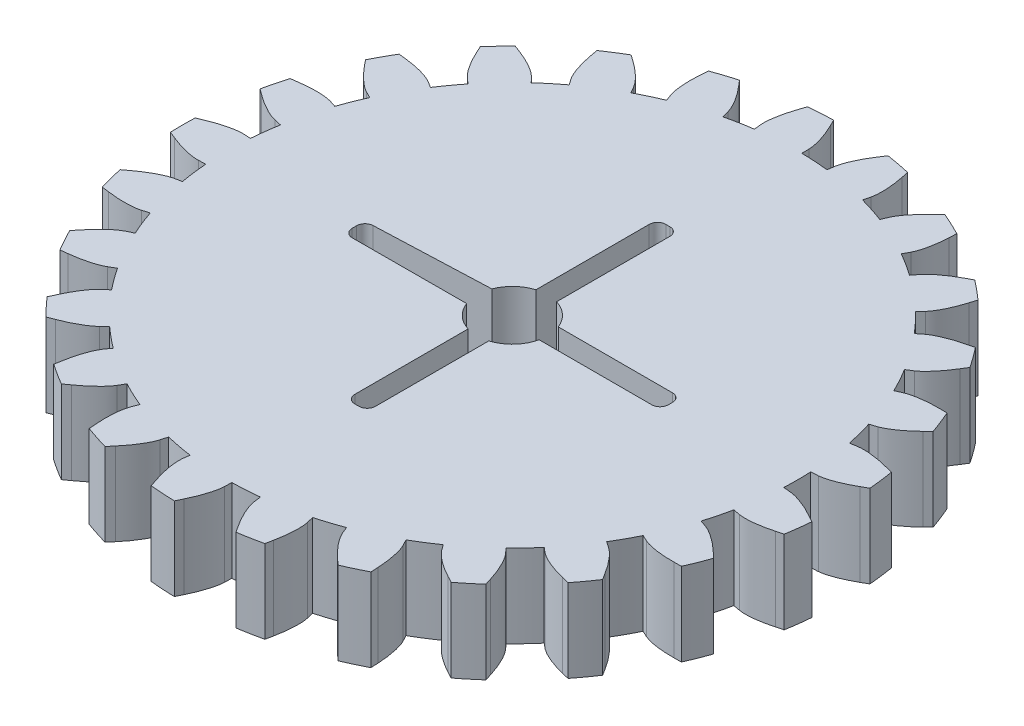
SolidWorks part; units mm, degrees
ref_plane "Front Plane" through (0, 0, 0) normal (0, 0, 1) x (1, 0, 0)
ref_plane "Top Plane" through (0, 0, 0) normal (0, 1, 0) x (1, 0, 0)
ref_plane "Right Plane" through (0, 0, 0) normal (1, 0, 0) x (0, 0, -1)
sketch "Sketch1" plane through (0, 0, 0) normal (0, 1, 0) x (1, 0, 0)
  line L0 (0, 30) -> (-129.8026, 30) construction
  line L1 (-99.777, -6.3159) -> (118.111, 72.9889) construction
  circle A0 centre (0, 0) radius 30
  circle A1 centre (0, 0) radius 28.1908
  dimension "D1" = 60
  dimension "D2" = 20
sketch "Sketch2" plane through (0, 0, 0) normal (0, 1, 0) x (1, 0, 0)
  line L0 (0, 0) -> (-9.6418, 26.4907) construction
  line L1 (-99.777, -6.3159) -> (118.111, 72.9889) construction
  line L2 (-9.6418, 26.4907) -> (0, 30)
  line L3 (-10.3543, 26.2204) -> (0, 0) construction
  line L4 (-10.3543, 26.2204) -> (-0.1021, 30.2689) construction
  line L5 (0, 0) -> (-11.0591, 25.931) construction
  line L6 (0, 0) -> (-11.7559, 25.6226) construction
  line L7 (-12.4441, 25.2955) -> (0, 0) construction
  line L8 (0, 0) -> (-13.1232, 24.95) construction
  line L9 (-8.9223, 26.7416) -> (0.088, 29.7479) construction
  line L10 (-11.0591, 25.931) -> (-0.2192, 30.554) construction
  line L11 (-11.7559, 25.6226) -> (-0.3523, 30.8547) construction
  line L12 (-12.4441, 25.2955) -> (-0.5023, 31.1703) construction
  line L13 (-6.7269, 27.3764) -> (0.2773, 29.0975) construction
  line L14 (-7.4643, 27.1846) -> (0.2256, 29.2961) construction
  line L15 (-5.9846, 27.5482) -> (0.319, 28.9176) construction
  line L16 (-8.1963, 26.973) -> (0.1629, 29.5131) construction
  line L17 (-5.2378, 27.6999) -> (0.3517, 28.7569) construction
  circle A0 centre (0, 0) radius 28.1908 construction
  arc A1 (-9.6418, 26.4907) -> (-10.3543, 26.2204) centre (0, 0) ccw
  arc A2 (-10.3543, 26.2204) -> (-11.0591, 25.931) centre (0, 0) ccw
  arc A3 (-11.0591, 25.931) -> (-11.7559, 25.6226) centre (0, 0) ccw
  arc A4 (-11.7559, 25.6226) -> (-12.4441, 25.2955) centre (0, 0) ccw
  arc A5 (-12.4441, 25.2955) -> (-13.1232, 24.95) centre (0, 0) ccw
  arc A6 (-9.6418, 26.4907) -> (-8.9223, 26.7416) centre (0, 0) cw
  arc A7 (-8.9223, 26.7416) -> (-8.1963, 26.973) centre (0, 0) cw
  arc A8 (-8.1963, 26.973) -> (-7.4643, 27.1846) centre (0, 0) cw
  arc A9 (-7.4643, 27.1846) -> (-6.7269, 27.3764) centre (0, 0) cw
  arc A10 (-6.7269, 27.3764) -> (-5.9846, 27.5482) centre (0, 0) cw
  arc A11 (-5.9846, 27.5482) -> (-5.2378, 27.6999) centre (0, 0) cw
  dimension "D1" = 10.2606
  dimension "D3" = 11.0226
  dimension "D8" = 11.7846
  dimension "D9" = 12.5466
  dimension "D10" = 13.3086
  dimension "D15" = 9.4986
  dimension "D16" = 8.7366
  dimension "D17" = 7.9746
  dimension "D18" = 7.2126
  dimension "D21" = 6.4506
  dimension "D22" = 5.6886
  dimension "D2" = 0.762
  dimension "D4" = 0.762
  dimension "D5" = 0.762
  dimension "D6" = 0.762
  dimension "D7" = 0.762
  dimension "D11" = 0.762
  dimension "D12" = 0.762
  dimension "D13" = 0.762
  dimension "D14" = 0.762
  dimension "D19" = 0.762
  dimension "D20" = 0.762
sketch "Sketch4" plane through (0, 0, 0) normal (0, 1, 0) x (1, 0, 0)
  line L0 (0, 0) -> (0, 39.7853) construction
  line L1 (0, 0) -> (-2.5084, 39.8703) construction
  circle A0 centre (0, 0) radius 28.1908 construction
  circle A1 centre (0, 0) radius 31.81
  circle A2 centre (0, 0) radius 30 construction
  spline S0 degree 3 poles (-0.5023, 31.1703) (-0.4025, 30.9674) (-0.2649, 30.6686) (-0.1033, 30.2758) (-0.0012, 30.0069) (0.0869, 29.7547) (0.1619, 29.52) (0.2247, 29.303) (0.2766, 29.1044) (0.3615, 28.7384) (0.4102, 28.4344) (0.4191, 28.1877) knots 0 0 0 0 0.215965 0.31411 0.405697 0.490726 0.569196 0.641109 0.706463 0.765259 1 1 1 1
  spline S1 degree 3 poles (-3.4083, 30.9875) (-3.4819, 30.7737) (-3.581, 30.46) (-3.692, 30.05) (-3.7597, 29.7704) (-3.8155, 29.5092) (-3.8604, 29.2669) (-3.8956, 29.0438) (-3.9221, 28.8402) (-3.9605, 28.4664) (-3.9707, 28.1588) (-3.9486, 27.9129) knots 0 0 0 0 0.215965 0.31411 0.405697 0.490726 0.569196 0.641109 0.706463 0.765259 1 1 1 1
  spline S2 degree 2 poles (-3.4083, 30.9875) (-3.2603, 31.434) (-3.1869, 31.65) knots 0 0 0 1 1 1
  spline S3 degree 2 poles (-0.5023, 31.1703) (-0.7051, 31.5947) (-0.805, 31.7998) knots 0 0 0 1 1 1
  dimension "D2" = 1.81
  dimension "D1" = 3.6
sketch "Sketch5" plane through (0, 0, 0) normal (0, 1, 0) x (1, 0, 0)
  circle A1 centre (0, 0) radius 27.5
  dimension "D1" = 55
extrude "Boss-Extrude1" add sketch "Sketch5" along normal blind 8
sketch "Sketch7" plane through (0, 0, 0) normal (0, 1, 0) x (1, 0, 0)
  line L0 (0.4191, 28.1877) -> (0.4191, 27.4968)
  circle A2 centre (0, 0) radius 27.5
  arc A3 (0.4191, 27.4968) -> (-3.8796, 27.225) centre (0, 0) ccw
  circle A5 centre (0, 0) radius 31.81
  arc A6 (-0.805, 31.7998) -> (-3.1869, 31.65) centre (0, 0) ccw
  spline S2 degree 2 poles (1699.805, -3589.3147) (-1700.698, 3653.3192) (1697.9844, -3589.3576) knots -126.549604 -126.549604 -126.549604 130.420166 130.420166 130.420166 only from (-0.5023, 31.1703) to (-0.805, 31.7998)
  spline S3 degree 2 poles (-0.5023, 31.1703) (-0.7051, 31.5947) (-0.805, 31.7998) knots 0 0 0 1 1 1
  spline S5 degree 3 poles (3998.5502, -48.5947) (-214.8655, 25.0361) (-15.2491, 67.1151) (-0.1033, 30.2758) (-0.0012, 30.0069) (0.0869, 29.7547) (0.1619, 29.52) (0.2247, 29.303) (0.2766, 29.1044) (3.7158, 14.2841) (-43.4125, -11.6598) (-3991.8986, -208.3943) knots -37.638042 -37.638042 -37.638042 -37.638042 0.215965 0.31411 0.405697 0.490726 0.569196 0.641109 0.706463 0.765259 15.172747 15.172747 15.172747 15.172747 only from (-0.5023, 31.1703) to (0.4191, 28.1877)
  spline S6 degree 3 poles (-0.5023, 31.1703) (-0.4025, 30.9674) (-0.2649, 30.6686) (-0.1033, 30.2758) (-0.0012, 30.0069) (0.0869, 29.7547) (0.1619, 29.52) (0.2247, 29.303) (0.2766, 29.1044) (0.3615, 28.7384) (0.4102, 28.4344) (0.4191, 28.1877) knots 0 0 0 0 0.215965 0.31411 0.405697 0.490726 0.569196 0.641109 0.706463 0.765259 1 1 1 1
  spline S8 degree 2 poles (-1236.5411, -3774.0539) (1229.4052, 3837.6657) (-1234.7295, -3773.8683) knots -126.549604 -126.549604 -126.549604 130.420166 130.420166 130.420166 only from (-3.4083, 30.9875) to (-3.1869, 31.65)
  spline S9 degree 2 poles (-3.4083, 30.9875) (-3.2603, 31.434) (-3.1869, 31.65) knots 0 0 0 1 1 1
  spline S10 degree 1 poles (-3.9486, 27.9129) (-3.8796, 27.225) knots 0 0 1 1
  spline S11 degree 3 poles (-3960.9299, -549.3628) (210.0333, 51.7685) (6.7171, 68.497) (-3.692, 30.05) (-3.7597, 29.7704) (-3.8155, 29.5092) (-3.8604, 29.2669) (-3.8956, 29.0438) (-3.9221, 28.8402) (-5.4768, 13.7058) (44.5316, -6.1268) (3986.5401, 293.5665) knots -37.638042 -37.638042 -37.638042 -37.638042 0.215965 0.31411 0.405697 0.490726 0.569196 0.641109 0.706463 0.765259 15.172747 15.172747 15.172747 15.172747 only from (-3.4083, 30.9875) to (-3.9486, 27.9129)
  spline S12 degree 3 poles (-3.4083, 30.9875) (-3.4819, 30.7737) (-3.581, 30.46) (-3.692, 30.05) (-3.7597, 29.7704) (-3.8155, 29.5092) (-3.8604, 29.2669) (-3.8956, 29.0438) (-3.9221, 28.8402) (-3.9605, 28.4664) (-3.9707, 28.1588) (-3.9486, 27.9129) knots 0 0 0 0 0.215965 0.31411 0.405697 0.490726 0.569196 0.641109 0.706463 0.765259 1 1 1 1
  dimension "D1" = 0
  dimension "D2" = 0
  dimension "D3" = 0
  dimension "D4" = 0
  dimension "D5" = 0
  dimension "D6" = 0
extrude "Boss-Extrude2" add sketch "Sketch7" along normal up to surface (8 mm away) up to face at (0, 8, 27.5)
sketch "Sketch8" plane through (0, 0, 0) normal (1, 0, 0) x (0, 0, -1)
  line L0 (0, 0) -> (-0.0016, 8) construction
  line L1 (27.4968, 8) -> (-27.5, 8) construction
pattern_circular "CirPattern2" count 25 over 360 about axis through (0, 8, 0) along (0, 1, 0) of "Boss-Extrude2"
sketch "Sketch9" plane through (0, 8, 0) normal (0, 1, 0) x (1, 0, 0)
  line L0 (0, -20.6825) -> (0, 17.5955) construction
  line L1 (19.9592, 0) -> (-20.7001, 0) construction
  line L2 (1, 3.2692) -> (1, 15)
  line L3 (1, -15) -> (-1, -15)
  line L4 (1, -15) -> (1, -3.2692)
  line L5 (1, 15) -> (-1, 15)
  line L6 (-1, -15) -> (-1, -3.2692)
  line L7 (1, -15) -> (-1, 15) construction
  line L8 (1, 15) -> (-1, -15) construction
  line L9 (14.9958, -0.7498) -> (3.3355, -0.7498)
  line L10 (14.9958, -0.7498) -> (14.9958, 1.2497)
  line L11 (14.9958, 1.2497) -> (3.1821, 1.2497)
  line L12 (-15, -1.25) -> (-15, 0.75)
  line L13 (14.9958, -0.7498) -> (-15, 0.75) construction
  line L14 (14.9958, 1.2497) -> (-15, -1.25) construction
  line L15 (-1, 3.2692) -> (-1, 15)
  line L19 (-3.1932, -1.221) -> (-15, -1.25)
  line L21 (-3.1932, 1.221) -> (-15, 0.75)
  arc A1 (-1, 3.2692) -> (-3.1932, 1.221) centre (0, 0) ccw
  arc A3 (-3.1932, -1.221) -> (-1, -3.2692) centre (0, 0) ccw
  arc A4 (1, -3.2692) -> (3.3355, -0.7498) centre (0, 0) ccw
  arc A5 (3.1821, 1.2497) -> (1, 3.2692) centre (0, 0) ccw
  dimension "D2" = 2
  dimension "D3" = 30
extrude "Cut-Extrude1" cut sketch "Sketch9" against normal through all
fillet "Fillet1" radius 0.8 8 edges at (1, 4, -15) (14.9958, 4, -1.2497) (-1, 4, 15) (1, 4, 15) (14.9958, 4, 0.7498) (-15, 4, 1.25) (-15, 4, -0.75) (-1, 4, -15)
equation "\"D3@Sketch2\"=\"D1@Sketch2\"+\"D2@Sketch2\""
equation "\"D4@Sketch2\"=\"D2@Sketch2\""
equation "\"D5@Sketch2\"=\"D2@Sketch2\""
equation "\"D6@Sketch2\"=\"D2@Sketch2\""
equation "\"D7@Sketch2\"=\"D2@Sketch2\""
equation "\"D8@Sketch2\"=\"D3@Sketch2\"+\"D2@Sketch2\""
equation "\"D9@Sketch2\"=\"D8@Sketch2\"+\"D2@Sketch2\""
equation "\"D12@Sketch2\"=\"D11@Sketch2\""
equation "\"D13@Sketch2\"=\"D12@Sketch2\""
equation "\"D14@Sketch2\"=\"D12@Sketch2\""
equation "\"D15@Sketch2\"=\"D1@Sketch2\"-\"D11@Sketch2\""
equation "\"D16@Sketch2\"=\"D15@Sketch2\"-\"D11@Sketch2\""
equation "\"D17@Sketch2\"=\"D16@Sketch2\"-\"D11@Sketch2\""
equation "\"D18@Sketch2\"=\"D17@Sketch2\"-\"D11@Sketch2\""
equation "\"D10@Sketch2\"=\"D1@Sketch2\" + 4*\"D11@Sketch2\""
equation "\"D21@Sketch2\"=\"D18@Sketch2\"-\"D11@Sketch2\""
equation "\"D22@Sketch2\"=\"D21@Sketch2\"-\"D11@Sketch2\""
